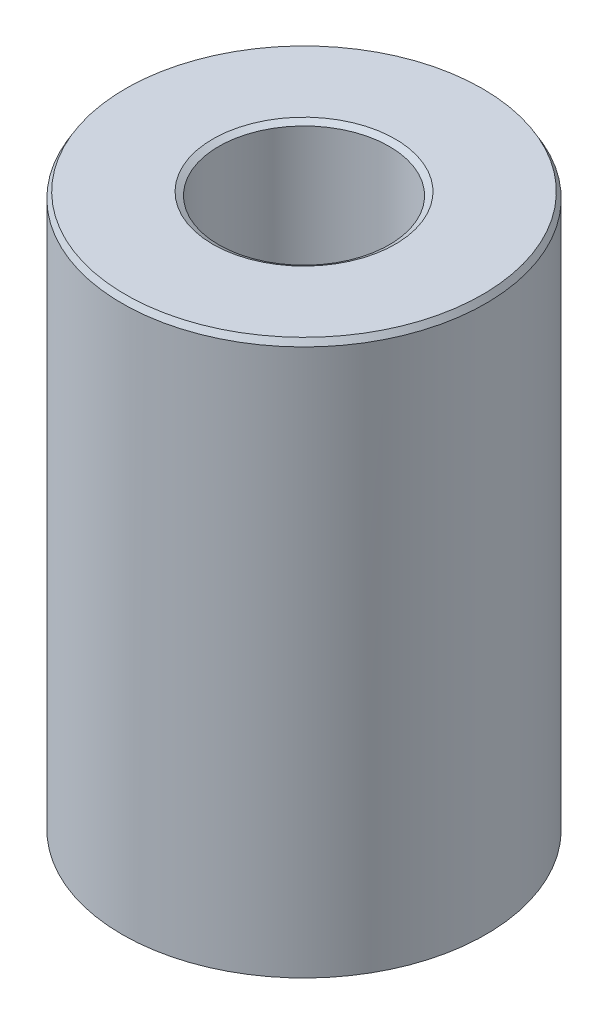
SolidWorks part; units mm, degrees
ref_plane "Front Plane" through (0, 0, 0) normal (0, 0, 1) x (1, 0, 0)
ref_plane "Top Plane" through (0, 0, 0) normal (0, 1, 0) x (1, 0, 0)
ref_plane "Right Plane" through (0, 0, 0) normal (1, 0, 0) x (0, 0, -1)
sketch "Sketch1" plane through (0, 0, 0) normal (0, 1, 0) x (1, 0, 0)
  circle A0 centre (0, 0) radius 35
  dimension "SLEEVE_OD" = 70
extrude "Boss-Extrude1" add sketch "Sketch1" along normal blind 106.9715
sketch "Sketch2" plane through (0, 0, 0) normal (0, 1, 0) x (1, 0, 0)
  circle A0 centre (0, 0) radius 16.4132
  dimension "BORE_D" = 32.8263
extrude "Cut-Extrude1" cut sketch "Sketch2" along normal through all
chamfer "Chamfer1" distance 1.1418 angle 30 4 edges at (0, 106.9715, 16.4132) (0, 0, 16.4132) (0, 0, 35) (0, 106.9715, 35) first distance on face at (0, 106.9715, 16.4132) first distance on face at (0, 0, 16.4132) first distance on face at (0, 106.9715, 35)
